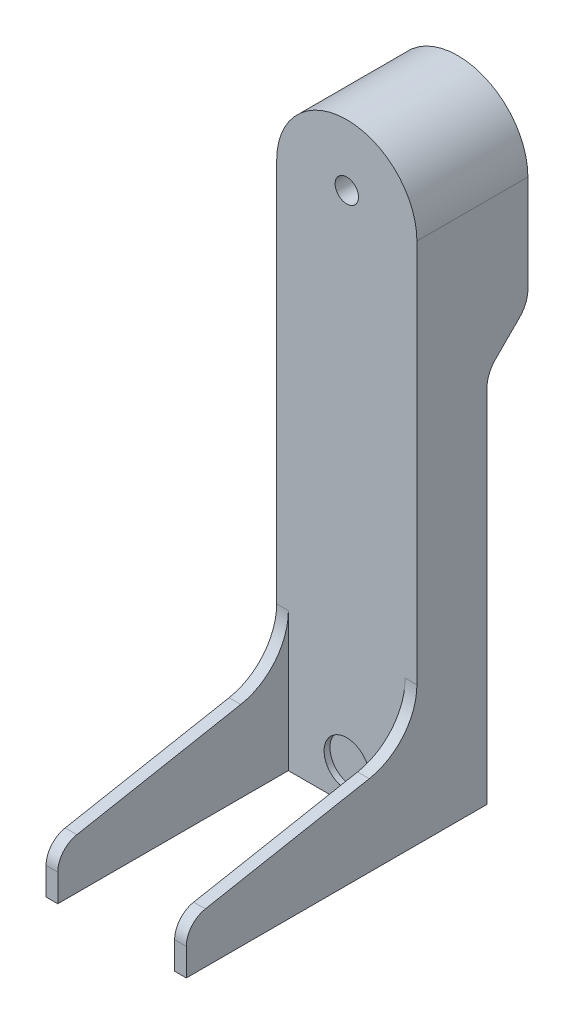
SolidWorks part; units mm, degrees
ref_plane "Front Plane" through (0, 0, 0) normal (0, 0, 1) x (1, 0, 0)
ref_plane "Top Plane" through (0, 0, 0) normal (0, 1, 0) x (1, 0, 0)
ref_plane "Right Plane" through (0, 0, 0) normal (1, 0, 0) x (0, 0, -1)
sketch "Sketch1" plane through (0, 0, 0) normal (1, 0, 0) x (0, 0, -1)
  line L0 (67, 21) -> (67, -151.1585)
  line L1 (67, -151.1585) -> (-11.9326, -166)
  line L2 (-11.9326, -166) -> (-11.9326, -182)
  line L3 (-11.9326, -182) -> (91, -182)
  line L4 (91, -182) -> (91, -54.3872)
  line L5 (91, -54.3872) -> (105, -40.3872)
  line L6 (105, -40.3872) -> (105, 21)
  line L7 (105, 21) -> (67, 21)
  line L8 (-85.9742, 0) -> (338.0667, 0) construction
  line L9 (-85.9742, -170) -> (338.0667, -170) construction
  point P13 (-35.8463, -200)
  point P14 (-28.6852, -192.8389)
  point P15 (105.8417, -169.821)
  point P16 (-85.9742, 0)
  point P17 (-85.9742, -200)
  point P19 (91, -36.1141)
  point P20 (-11.0448, -188.8899)
  point P21 (67, -182.2748)
  point P22 (-11.393, -196.2014)
  point P23 (67, -151.1585)
  point P24 (-10.9598, -164.7781)
  point P25 (-11.9326, -194)
  dimension "D1" = 170
  dimension "D2" = 67
  dimension "D3" = 38
  dimension "D4" = 24
  dimension "D5" = 21
  dimension "D6" = 45
  dimension "D7" = 12
extrude "Boss-Extrude1" add sketch "Sketch1" along normal mid plane 48
fillet "Fillet1" 2 edges at (-24, 21, -86) (24, 21, -86) type full round first side face at (-24, -91.7416, -62.7669) second side face at (24, -91.7416, -62.7669) middle face at (0, 21, -86)
sketch "Sketch2" plane through (0, 0, 0) normal (0, 1, 0) x (1, 0, 0)
  line L0 (24, -11.9326) -> (-24, -11.9326) construction
  line L1 (-24, 67) -> (24, 67) construction
  line L2 (24, -11.9326) -> (-24, -11.9326) construction
  line L3 (-24, 67) -> (24, 67) construction
  line L5 (-20, 67) -> (20, 67)
  line L6 (-20, 67) -> (-20, -11.9326)
  line L7 (-20, -11.9326) -> (20, -11.9326)
  line L8 (20, 67) -> (20, -11.9326)
  point P8 (0, 67)
  dimension "D1" = 40
extrude "Cut-Extrude1" cut sketch "Sketch2" against normal through all
sketch "Sketch3" plane through (0, 0, 0) normal (0, 0, 1) x (1, 0, 0)
  circle A0 centre (0, 0) radius 4
  dimension "D1" = 8
extrude "Cut-Extrude2" cut sketch "Sketch3" against normal through all
fillet "Fillet2" radius 10 2 edges at (0, -54.3872, -91) (0, -40.3872, -105)
fillet "Fillet3" radius 20 2 edges at (22, -151.1585, -67) (-22, -151.1585, -67)
fillet "Fillet4" radius 8 2 edges at (-22, -166, 11.9326) (22, -166, 11.9326)
sketch "Sketch4" plane through (0, 0, 0) normal (0, 0, 1) x (1, 0, 0)
  circle A0 centre (0, -170) radius 7.7662
  dimension "D1" = 170
extrude "Cut-Extrude3" cut sketch "Sketch4" against normal blind 2 from surface starting at face at (-4, 0, -67)
equation "\"spine_distance_to_axle\"= 65mm"
equation "\"spine_depth\"= 42mm"
equation "\"aluminum_thickness\"= 2mm"
equation "\"pulley_center_to_center_distance\"= 170"
equation "\"D1@Sketch1\"=\"pulley_center_to_center_distance\""
equation "\"D2@Sketch1\"=\"spine_distance_to_axle\"+\"aluminum_thickness\""
equation "\"D3@Sketch1\"=\"spine_depth\"-(\"aluminum_thickness\"*2)"
equation "\"D1@Boss-Extrude1\"=\"width\""
equation "\"D1@Sketch4\"=\"pulley_center_to_center_distance\""
